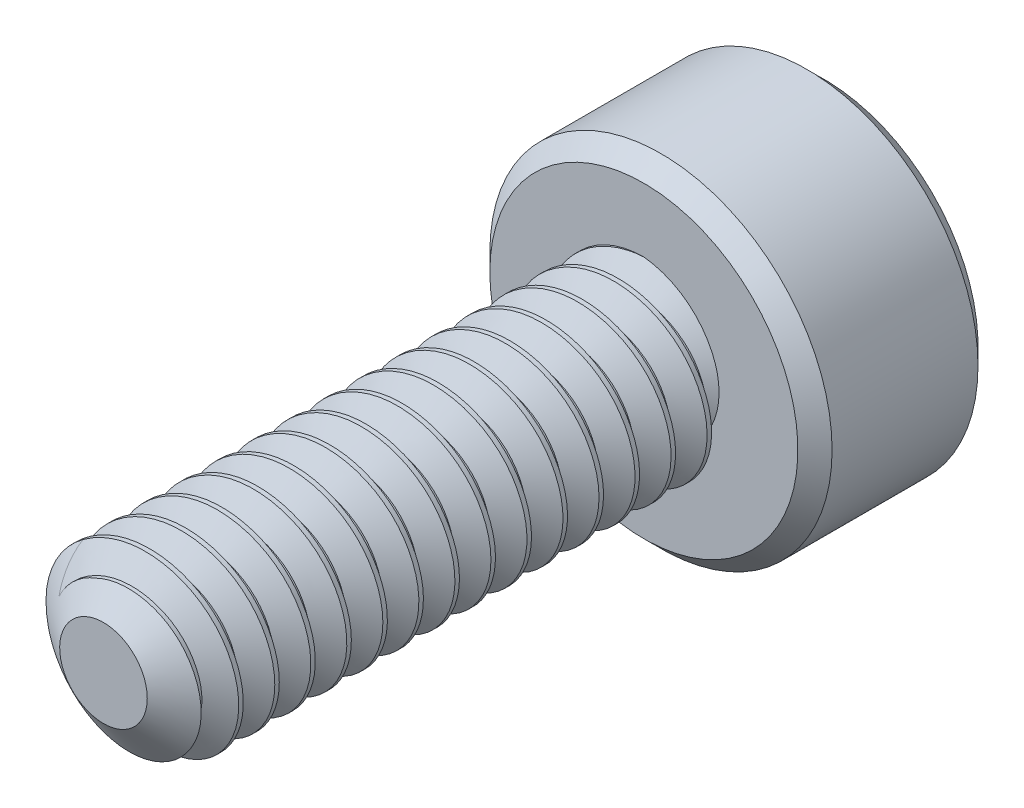
SolidWorks part; units mm, degrees
other "DetailItem1"
ref_plane "Front Plane" through (0, 0, 0) normal (0, 0, 1) x (1, 0, 0)
ref_plane "Top Plane" through (0, 0, 0) normal (0, 1, 0) x (1, 0, 0)
ref_plane "Right Plane" through (0, 0, 0) normal (1, 0, 0) x (0, 0, -1)
sketch "Sketch1" plane through (0, 0, 0) normal (0, 0, 1) x (1, 0, 0)
  circle A0 centre (0, 0) radius 1
  dimension "OD" = 2
extrude "Extrude1" add sketch "Sketch1" against normal blind 6
sketch "Sketch2" plane through (0, 0, 0) normal (0, 0, 1) x (1, 0, 0)
  circle A0 centre (0, 0) radius 1 construction
  circle A1 centre (0, 0) radius 1
curve "Helix/Spiral1" pitch 0.4 height 6.4 radius 1 centre (0, 0, 0) axis (0, 0, -1) start towards (0, 1, 0) parameters "pitch"=0.4
sketch "Sketch3" plane through (0, 0, 0) normal (1, 0, 0) x (0, 0, -1)
  line L0 (-0.35, 1) -> (-0.2, 0.7402)
  line L1 (-0.2, 0.7402) -> (-0.15, 0.7402)
  line L2 (-0.15, 0.7402) -> (0, 1)
  line L3 (-0.35, 1) -> (0, 1)
  line L4 (-0.175, 1) -> (-0.175, 0.7402) construction
  line L5 (-0.275, 0.8701) -> (-0.075, 0.8701) construction
  line L6 (0, 1) -> (0, -1) construction
  dimension "D1" = 0.05
  dimension "D2" = 0.2
  dimension "D3" = 60
sweep "Cut-Sweep1" cut profiles "Sketch3" path "Helix/Spiral1"
sketch "Sketch4" plane through (0, 0, 0) normal (1, 0, 0) x (0, 0, -1)
  line L0 (0.3598, 1) -> (0, 0.4862)
  line L1 (0, 0.4862) -> (0, 1)
  line L2 (0.3598, 1) -> (0, 1)
  line L3 (-0.35, 1) -> (0, 1) construction
  line L4 (0, 0) -> (7.0209, 0) construction
  dimension "D1" = 55
  dimension "D2" = 0.254
revolve "Cut-Revolve1" cut sketch "Sketch4" angle 360 about L4
sketch "Sketch6" plane through (0, 0, -6) normal (0, 0, -1) x (-1, 0, 0)
  circle A0 centre (0, 0) radius 1.9
  dimension "head dia" = 3.8
extrude "Extrude2" add sketch "Sketch6" along normal blind 2
sketch "Sketch7" plane through (0, 0, -8) normal (0, 0, -1) x (-1, 0, 0)
  line L1 (0, 0.866) -> (-0.75, 0.433)
  line L2 (-0.75, 0.433) -> (-0.75, -0.433)
  line L3 (-0.75, -0.433) -> (0, -0.866)
  line L4 (0, -0.866) -> (0.75, -0.433)
  line L5 (0.75, -0.433) -> (0.75, 0.433)
  line L6 (0.75, 0.433) -> (0, 0.866)
  circle A0 centre (0, 0) radius 0.75 construction
  dimension "hex dia" = 1.5
extrude "Cut-Extrude1" cut sketch "Sketch7" against normal blind 1.125
sketch "Sketch8" plane through (0, 0, -8) normal (0, 0, -1) x (-1, 0, 0)
  circle A0 centre (0, 0) radius 0.866
extrude "Cut-Extrude2" cut sketch "Sketch8" against normal through all draft 45
chamfer "Chamfer1" distance 0.19 angle 45 2 edges at (-1.9, 0, -8) (-1.9, 0, -6)
sketch "Sketch10" plane through (0, 0, -6) normal (0, 0, 1) x (1, 0, 0)
  circle A1 centre (0, 0) radius 1
  circle A2 centre (0, 0) radius 1
  dimension "D1" = 0
ref_plane "Plane1" through (0, 0, 0) normal (0, 0, 1) x (1, 0, 0)
extrude "partial thread" [suppressed] add sketch "Sketch10" along normal up to surface (2 mm away) separate body up to plane "Plane1"
chamfer "Chamfer2" [suppressed] distance 0.04 angle 45
combine bodies "Combine1" [suppressed] operation type add bodies to combine 107 108
sketch "Sketch9" plane through (0, 0, 0) normal (1, 0, 0) x (0, 0, -1)
  line L0 (0, 1) -> (0, -1) construction
  line L1 (1, 1) -> (1, -1) construction
  dimension "D1" = 1
equation "\"D3@Helix/Spiral1\" = \"screw length@Extrude1\"+\"pitch@Helix/Spiral1\""
equation "\"D1@Sketch3\" = \"pitch@Helix/Spiral1\"*.125"
equation "\"D2@Sketch3\" = \"pitch@Helix/Spiral1\"*.5"
equation "\"D1@Cut-Extrude1\" = \"hex dia@Sketch7\"*.75"
equation "\"D1@Chamfer1\" = \"head dia@Sketch6\"*.05"
equation "\"D1@Sketch9\" = \"pitch@Helix/Spiral1\"*2.5"
equation "\"D1@Chamfer2\"=\"OD@Sketch1\"*.02"
